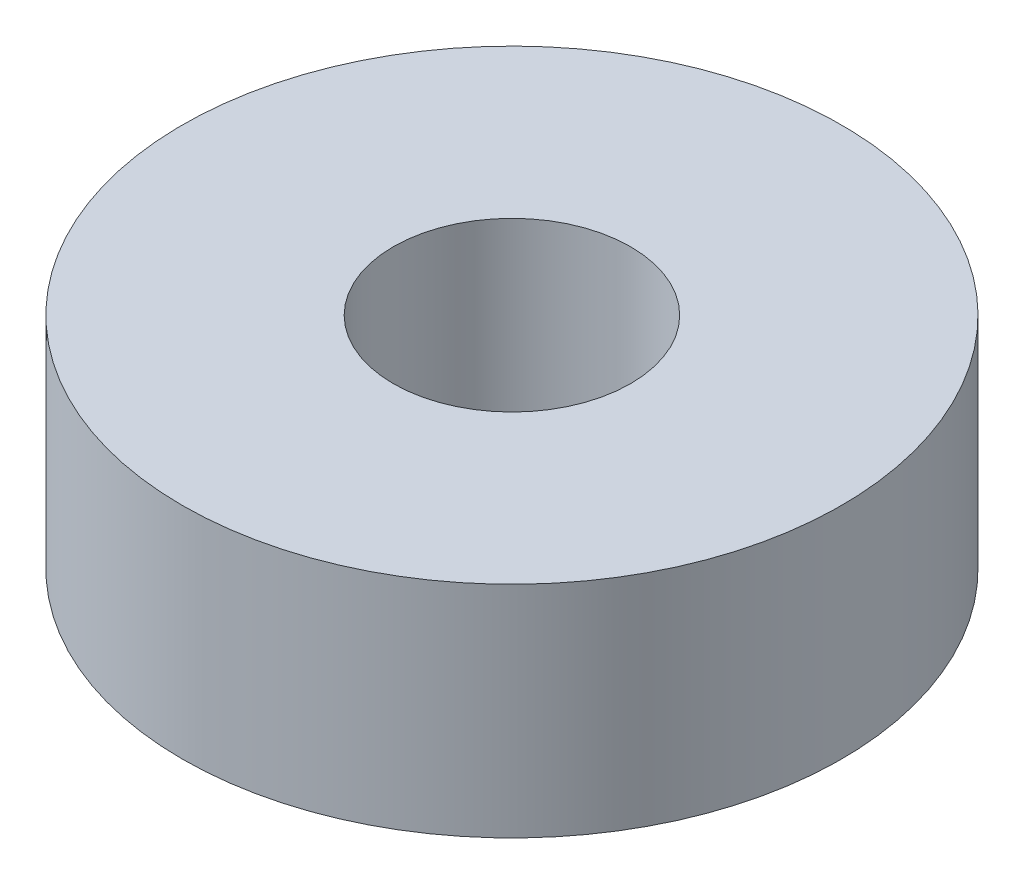
SolidWorks part; units mm, degrees
ref_plane "前基準面" through (0, 0, 0) normal (0, 0, 1) x (1, 0, 0)
ref_plane "上基準面" through (0, 0, 0) normal (0, 1, 0) x (1, 0, 0)
ref_plane "右基準面" through (0, 0, 0) normal (1, 0, 0) x (0, 0, -1)
ref_axis "基準軸1" through (0, -55, 0) along (0, 1, 0)
ref_axis "基準軸2" through (-88.99, 0, 0) along (1, 0, 0)
ref_axis "基準軸3" through (0, 0, 55) along (0, 0, -1)
sketch "草圖1" plane through (0, 0, 0) normal (0, 1, 0) x (1, 0, 0)
  circle A0 centre (0, 0) radius 2.7
  circle A1 centre (0, 0) radius 7.5
  dimension "D1" = 5.4
  dimension "D2" = 15
extrude "填料-伸長1" add sketch "草圖1" along normal blind 5
